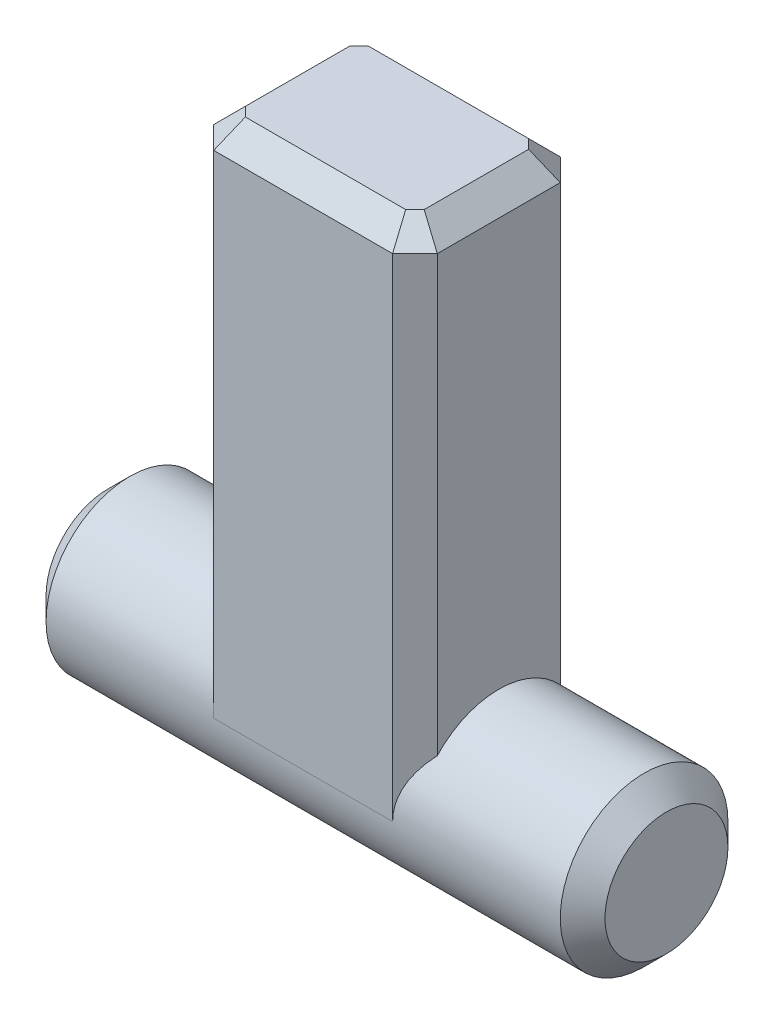
SolidWorks part; units mm, degrees
ref_plane "前视基准面" through (0, 0, 0) normal (0, 0, 1) x (1, 0, 0)
ref_plane "上视基准面" through (0, 0, 0) normal (0, 1, 0) x (1, 0, 0)
ref_plane "右视基准面" through (0, 0, 0) normal (1, 0, 0) x (0, 0, -1)
other "Configuration Table"
sketch "草图1" plane through (0, 0, 0) normal (0, 1, 0) x (1, 0, 0)
  circle A0 centre (0, 0) radius 50
  dimension "D1" = 100
extrude "凸台-拉伸1" add sketch "草图1" along normal blind 50
sketch "草图2" plane through (0, 50, 0) normal (0, 1, 0) x (1, 0, 0)
  line L0 (-50, 0) -> (50, 0)
  line L1 (25, 43.3013) -> (-25, -43.3013)
  line L2 (25, -43.3013) -> (-25, 43.3013)
  circle A1 centre (0, 0) radius 50
  circle A2 centre (0, 0) radius 50
  point P11 (0, 0)
  circle M3 centre (0, 0) radius 50
  dimension "D1" = 0
  dimension "D2" = 3
extrude "切除-拉伸2" cut sketch "草图2" against normal through all contours L2 L1 M3 | L1 L0 M3 | L2 L0 M3 | L0 L2 M3 | L1 L0 M3 region at (-27.5664, 50, -15.9155) region at (-27.5664, 50, 15.9155) region at (27.5664, 50, -15.9155) region at (0, 50, -31.831) region at (27.5664, 50, 15.9155)
sketch "草图3" plane through (0, 50, 0) normal (0, 1, 0) x (1, 0, 0)
  line L0 (-8.6603, -15) -> (8.6603, -15)
  line L1 (0, 0) -> (-25, -43.3013) construction
  line L2 (25, -43.3013) -> (0, 0) construction
  line L5 (25, -43.3013) -> (0, 0)
  line L6 (0, 0) -> (-25, -43.3013)
  line L7 (25, -43.3013) -> (0, 0)
  line L8 (0, 0) -> (-25, -43.3013)
  circle A0 centre (0, 0) radius 15
  arc A2 (-25, -43.3013) -> (25, -43.3013) centre (0, 0) ccw
  arc A3 (-25, -43.3013) -> (25, -43.3013) centre (0, 0) ccw
  line M2 (25, -43.3013) -> (0, 0)
  line M3 (0, 0) -> (-25, -43.3013)
  dimension "D1" = 30
  dimension "D2" = 0
extrude "切除-拉伸3" cut sketch "草图3" against normal through all contours A0 L7 M3 | A0 L0 M2 | A0 L8 L0 region at (-6.0821, 50, 14.3903) region at (6.0821, 50, 14.3903) region at (0, 50, 9.5493)
fillet "圆角1" radius 2 4 edges at (-8.6603, 25, 15) (-25, 25, 43.3013) (25, 25, 43.3013) (8.6603, 25, 15)
chamfer "倒角1" distance 0.6 angle 45 8 edges at (0, 0, 15) (-8.5056, 0, 15.2679) (8.5056, 0, 15.2679) (-16.6084, 0, 28.7666) (16.6084, 0, 28.7666) (-24.1678, 0, 43.0909) (24.1678, 0, 43.0909) (0, 0, 50)
shell "抽壳1" thickness 1.2 removed face at (0, 50, 29.9064)
sketch "草图4" plane through (0, 0, 0) normal (1, 0, 0) x (0, 0, -1)
  line L0 (-16.3, 0) -> (-41.8331, 0) construction
  line L1 (-44.5, -3) -> (-44.5, 0)
  line L2 (-49.4, 0) -> (-43.7737, 0) construction
  line L3 (-41.5, -3) -> (-41.5, 0)
  line L4 (-43.7737, 0) -> (-41.8331, 0) construction
  line L5 (-44.5, 0) -> (-41.5, 0)
  circle A0 centre (-43, -3) radius 1.5
  dimension "D2" = 3
  dimension "D1" = 43
  dimension "D3" = 3
extrude "凸台-拉伸2" add sketch "草图4" along normal blind 2 and the other way blind 2 contours A0 L3 L5 L1 | A0 region at (0, -0.9417, 43) region at (0, -3, 43)
sketch "草图5" plane through (2, 0, 0) normal (1, 0, 0) x (0, 0, -1)
  circle A0 centre (-43, -3) radius 1.5
  arc A1 (-44.5, -3) -> (-41.5, -3) centre (-43, -3) ccw construction
extrude "凸台-拉伸3" add sketch "草图5" along normal blind 3
mirror "镜向1" about plane through (0, 0, 0) normal (1, 0, 0) of "凸台-拉伸3"
sketch "草图6" plane through (0, 0, 0) normal (1, 0, 0) x (0, 0, -1)
  line L0 (-41.5331, 50) -> (-16, 50) construction
  line L1 (-41.5331, 50) -> (-16, 50) construction
  line L2 (-16, 0.6) -> (-15, 0.6) construction
  line L3 (-15, 0.6) -> (-15, 50) construction
  line L4 (-15, 50) -> (-16, 50) construction
  line L5 (-41.5331, 50) -> (-41.5331, 0.6) construction
  line L6 (-41.5331, 0.6) -> (-16, 0.6) construction
  line L7 (-16, 50) -> (-41.5331, 50) construction
  line L8 (-16, 0.6) -> (-15, 0.6)
  line L9 (-15, 0.6) -> (-15, 50)
  line L10 (-15, 50) -> (-16, 50)
  line L11 (-41.5331, 50) -> (-41.5331, 0.6)
  line L12 (-41.5331, 0.6) -> (-16, 0.6)
  line L13 (-16, 50) -> (-41.5331, 50)
  circle A0 centre (-43, -3) radius 53
extrude "切除-拉伸4" cut sketch "草图6" against normal through all and the other way through all contours A0 L9 L10 L13 L11 region at (0, 47.6343, 21.8872)
sketch "草图7" plane through (0, 1.2, 0) normal (0, 1, 0) x (1, 0, 0)
  line L0 (2, -44.5) -> (2, -41.5) construction
  line L1 (2, -44.5) -> (2, -41.5) construction
  line L2 (-2, -44.5) -> (-2, -41.5) construction
  line L3 (-2, -44.5) -> (-2, -41.5) construction
  line L5 (-2, -41.5) -> (2, -41.5)
  line L6 (-2, -41.5) -> (-2, -44.5)
  line L7 (-2, -44.5) -> (2, -44.5)
  line L8 (2, -41.5) -> (2, -44.5)
  line L9 (-3.2, -40.3) -> (3.2, -40.3)
  line L10 (-3.2, -40.3) -> (-3.2, -45.7)
  line L11 (-3.2, -45.7) -> (3.2, -45.7)
  line L12 (3.2, -40.3) -> (3.2, -45.7)
  dimension "D1" = 1.2
  dimension "D2" = 1.2
  dimension "D3" = 1.2
  dimension "D4" = 1.2
extrude "凸台-拉伸4" add sketch "草图7" along normal blind 3
sketch "草图8" plane through (0, 0, 0) normal (0, -1, 0) x (1, 0, 0)
  line L1 (-29.8484, 54.1288) -> (31.8342, 54.1288)
  line L2 (-29.8484, 54.1288) -> (-29.8484, 4.773)
  line L3 (-29.8484, 4.773) -> (31.8342, 4.773)
  line L4 (31.8342, 54.1288) -> (31.8342, 4.773)
extrude "切除-拉伸5" cut sketch "草图8" against normal through all
sketch "草图9" plane through (0, 0, 0) normal (0, 1, 0) x (1, 0, 0)
  line L4 (-2, -44.5) -> (2, -44.5)
  line L5 (2, -44.5) -> (2, -41.5)
  line L6 (2, -41.5) -> (-2, -41.5)
  line L7 (-2, -41.5) -> (-2, -44.5)
  line L8 (-2, -44.5) -> (2, -44.5)
  line L9 (2, -44.5) -> (2, -41.5)
  line L10 (2, -41.5) -> (-2, -41.5)
  line L11 (-2, -41.5) -> (-2, -44.5)
  dimension "D1" = 0
extrude "凸台-拉伸5" add sketch "草图9" along normal blind 6.2
chamfer "倒角2" distance 0.4 angle 45 4 edges at (2, 1.6, 44.5) (-2, 1.6, 44.5) (-2, 1.6, 41.5) (2, 1.6, 41.5)
chamfer "倒角3" distance 0.4 angle 45 8 edges at (-1.8, 6.2, 44.3) (-2, 6.2, 43) (-1.8, 6.2, 41.7) (0, 6.2, 41.5) (1.8, 6.2, 41.7) (2, 6.2, 43) (1.8, 6.2, 44.3) (0, 6.2, 44.5)
chamfer "倒角4" distance 0.4 angle 45 2 edges at (5, -3, 41.5) (-5, -3, 41.5)
